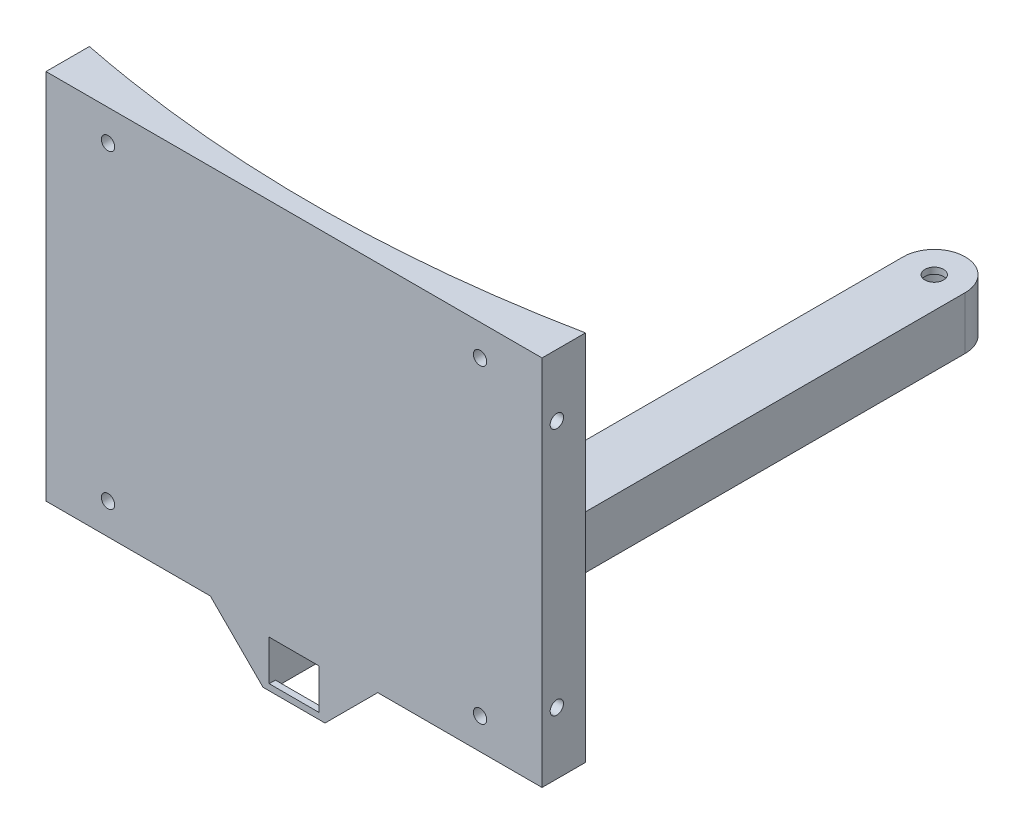
SolidWorks part; units mm, degrees
ref_plane "Front Plane" through (0, 0, 0) normal (0, 0, 1) x (1, 0, 0)
ref_plane "Top Plane" through (0, 0, 0) normal (0, 1, 0) x (1, 0, 0)
ref_plane "Right Plane" through (0, 0, 0) normal (1, 0, 0) x (0, 0, -1)
sketch "Sketch1" plane through (0, 0, 0) normal (0, 1, 0) x (1, 0, 0)
  line L0 (0, -200) -> (0, 0) construction
  line L1 (-225, -136.7187) -> (225, -136.7187) construction
  parabola Q0 (-225, -136.7187) -> (225, -136.7187) focus (0, 0) apex (0, -200) construction
  spline S0 degree 1 poles (-225.2451, -137.1545) (225.2451, -137.1545) knots 0 0 1 1 construction
  spline S1 degree 3 poles (-225.2451, -137.1545) (-222.9082, -138.4691) (-218.2041, -141.0739) (-208.8273, -146.1009) (-197.0951, -152.0818) (-183.0206, -158.7616) (-164.2523, -167.0094) (-140.7912, -176.0823) (-112.6357, -184.9909) (-84.4784, -191.9202) (-46.9336, -198.52) (0, -201.82) (46.9336, -198.52) (84.4784, -191.9202) (112.6357, -184.9909) (140.7912, -176.0823) (164.2523, -167.0094) (183.0206, -158.7616) (197.0951, -152.0818) (208.8273, -146.1009) (218.2041, -141.0739) (222.9082, -138.4691) (225.2451, -137.1545) knots 0.496023 0.496023 0.496023 0.496023 0.496147 0.496271 0.49652 0.496768 0.497017 0.497514 0.498011 0.498508 0.499006 0.5 0.500994 0.501492 0.501989 0.502486 0.502983 0.503232 0.50348 0.503729 0.503853 0.503977 0.503977 0.503977 0.503977 construction
  dimension "D1" = 450
  dimension "D2" = 200
  dimension "D3" = 0.5
sketch "Sketch4" plane through (0, 0, 0) normal (0, 1, 0) x (1, 0, 0)
  line L0 (-80, -157.049) -> (-80, -357.049) construction
  line L1 (80, -173.7313) -> (80, -373.7313) construction
  line L2 (0, -200) -> (0, 0) construction
  line L3 (-80, -192.5099) -> (-80, -206.5)
  line L4 (80, -192.5099) -> (80, -206.5)
  line L5 (-80, -206.5) -> (80, -206.5)
  spline S0 degree 3 poles (1573.6078, -1009.9911) (-454.8299, 36.4001) (-329.3751, -81.4734) (-208.8273, -146.1009) (-197.0951, -152.0818) (-183.0206, -158.7616) (-164.2523, -167.0094) (-140.7912, -176.0823) (-112.6357, -184.9909) (-84.4784, -191.9202) (-46.9336, -198.52) (0, -201.82) (46.9336, -198.52) (84.4784, -191.9202) (112.6357, -184.9909) (140.7912, -176.0823) (164.2523, -167.0094) (183.0206, -158.7616) (197.0951, -152.0818) (208.8273, -146.1009) (329.3765, -81.4727) (454.8329, 36.4029) (-1573.6829, -1010.0298) knots 0.490128 0.490128 0.490128 0.490128 0.496147 0.496271 0.49652 0.496768 0.497017 0.497514 0.498011 0.498508 0.499006 0.5 0.500994 0.501492 0.501989 0.502486 0.502983 0.503232 0.50348 0.503729 0.503853 0.509872 0.509872 0.509872 0.509872 only from (-225.2451, -137.1545) to (225.2451, -137.1545) construction
  spline S1 degree 3 poles (-80, -192.5099) (-72.1067, -194.0866) (-45.4407, -198.6249) (0, -201.82) (45.4407, -198.6249) (72.1067, -194.0866) (80, -192.5099) knots 0.498588 0.498588 0.498588 0.498588 0.499006 0.5 0.500994 0.501412 0.501412 0.501412 0.501412
  point P2 (0, -206.5)
  point P14 (0, -200.5)
  dimension "D2" = 80
  dimension "D3" = 80
  dimension "D1" = 6
extrude "Boss-Extrude3" add sketch "Sketch4" along normal blind 120
sketch "Sketch6" plane through (0, 0, 0) normal (0, -1, 0) x (1, 0, 0)
  line L0 (10, 0) -> (10, 206.5)
  line L1 (-80, 206.5) -> (80, 206.5) construction
  line L2 (10, 206.5) -> (-10, 206.5)
  line L3 (-10, 206.5) -> (-10, 0)
  line L4 (0, 200) -> (0, 0) construction
  arc A0 (10, 0) -> (-10, 0) centre (0, 0) cw
  dimension "D1" = 10
extrude "Boss-Extrude4" add sketch "Sketch6" along normal blind 2
sketch "Sketch7" plane through (0, -2, 0) normal (0, -1, 0) x (1, 0, 0)
  line L0 (8, 0) -> (8, 204.5)
  line L1 (8, 204.5) -> (-8, 204.5)
  line L2 (-8, 204.5) -> (-8, 0)
  line L3 (10, 0) -> (10, 206.5)
  line L4 (10, 206.5) -> (-10, 206.5)
  line L5 (-10, 206.5) -> (-10, 0)
  line L6 (10, 0) -> (10, 206.5)
  line L7 (10, 206.5) -> (-10, 206.5)
  line L8 (-10, 206.5) -> (-10, 0)
  arc A0 (-8, 0) -> (8, 0) centre (0, 0) ccw
  arc A1 (-10, 0) -> (10, 0) centre (0, 0) ccw
  arc A2 (-10, 0) -> (10, 0) centre (0, 0) ccw
  dimension "D1" = 0
  dimension "D2" = 2
extrude "Boss-Extrude5" add sketch "Sketch7" along normal blind 15
sketch "Sketch8" plane through (0, 0, 206.5) normal (0, 0, 1) x (1, 0, 0)
  line L0 (8, -15) -> (-8, -15)
  line L1 (10, -17) -> (-10, -17) construction
  line L2 (10, -17) -> (10, 0) construction
  line L3 (10, 0) -> (-10, 0) construction
  line L4 (-10, -17) -> (-10, 0) construction
  line L5 (-8, -15) -> (-8, -2)
  line L6 (8, -2) -> (-8, -2)
  line L7 (8, -15) -> (8, -2)
  dimension "D1" = 2
extrude "Cut-Extrude2" cut sketch "Sketch8" against normal blind 15
sketch "Sketch10" plane through (80, 0, 0) normal (1, 0, 0) x (0, 0, -1)
  circle A0 centre (-201.7286, 100) radius 2.15
  circle A1 centre (-201.7286, 20) radius 2.15
  dimension "D1" = 4.3
extrude "Cut-Extrude3" cut sketch "Sketch10" against normal blind 10
mirror "Mirror1" about plane through (0, 0, 0) normal (1, 0, 0) of "Cut-Extrude3"
sketch "Sketch11" plane through (0, 0, 206.5) normal (0, 0, 1) x (1, 0, 0)
  circle A0 centre (60, 110) radius 2.15
  circle A1 centre (60, 10) radius 2.15
  circle A2 centre (-60, 110) radius 2.15
  circle A3 centre (-60, 10) radius 2.15
  dimension "D1" = 4.3
extrude "Cut-Extrude4" cut sketch "Sketch11" against normal blind 7
sketch "Sketch12" plane through (0, 0, 0) normal (0, 1, 0) x (1, 0, 0)
  circle A0 centre (0, 0) radius 3
  dimension "D1" = 6
extrude "Cut-Extrude5" cut sketch "Sketch12" against normal blind 7
sketch "Sketch14" plane through (0, 0, 206.5) normal (0, 0, 1) x (1, 0, 0)
  line L0 (10, 0) -> (10, -17) construction
  line L1 (10, -6.6126) -> (10, -9.2583)
  circle A0 centre (11.5, -7.9355) radius 1.5
  arc A1 (10, -9.2583) -> (10, -6.6126) centre (11.5, -7.9355) ccw
  dimension "D1" = 3
  dimension "D2" = 4
chamfer "Chamfer1" distance 17 angle 45 2 edges at (10, 0, 203.4376) (-10, 0, 203.4376)
fillet "Fillet1" radius 13 2 edges at (-10, -8.5, 200.3752) (10, -8.5, 200.3752)
equation "\"Focus\"= 200mm"
equation "\"Dish Width\"= 450mm"
equation "\"Plate Thickness\"= 0.5mm"
equation "\"D1@Sketch1\"=\"Dish Width\""
equation "\"D2@Sketch1\"=\"Focus\""
equation "\"D3@Sketch1\"=\"Plate Thickness\""
equation "\"D3@Sketch4\"=\"D2@Sketch4\""
